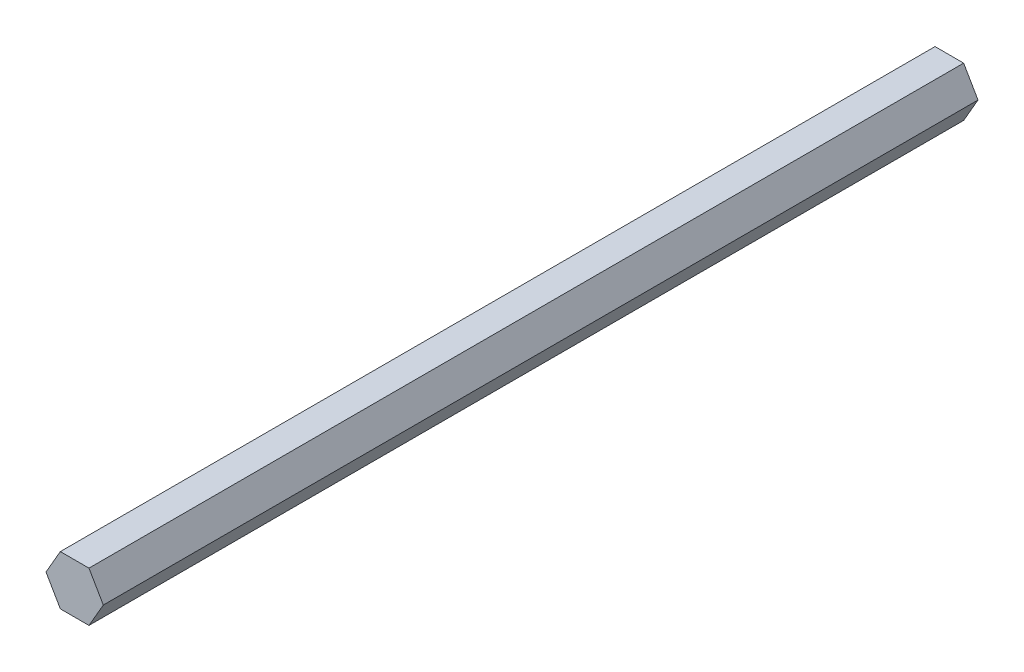
SolidWorks part; units mm, degrees
ref_plane "Front Plane" through (0, 0, 0) normal (0, 0, 1) x (1, 0, 0)
ref_plane "Top Plane" through (0, 0, 0) normal (0, 1, 0) x (1, 0, 0)
ref_plane "Right Plane" through (0, 0, 0) normal (1, 0, 0) x (0, 0, -1)
sketch "Sketch1" plane through (0, 0, 0) normal (0, 0, 1) x (1, 0, 0)
  line L1 (-7.3323, 0) -> (-3.6662, -6.35)
  line L2 (-3.6662, -6.35) -> (3.6662, -6.35)
  line L3 (3.6662, -6.35) -> (7.3323, 0)
  line L4 (7.3323, 0) -> (3.6662, 6.35)
  line L5 (3.6662, 6.35) -> (-3.6662, 6.35)
  line L6 (-3.6662, 6.35) -> (-7.3323, 0)
  circle A0 centre (0, 0) radius 6.35 construction
  dimension "D1" = 12.7
extrude "Boss-Extrude1" add sketch "Sketch1" along normal blind 223.8375
